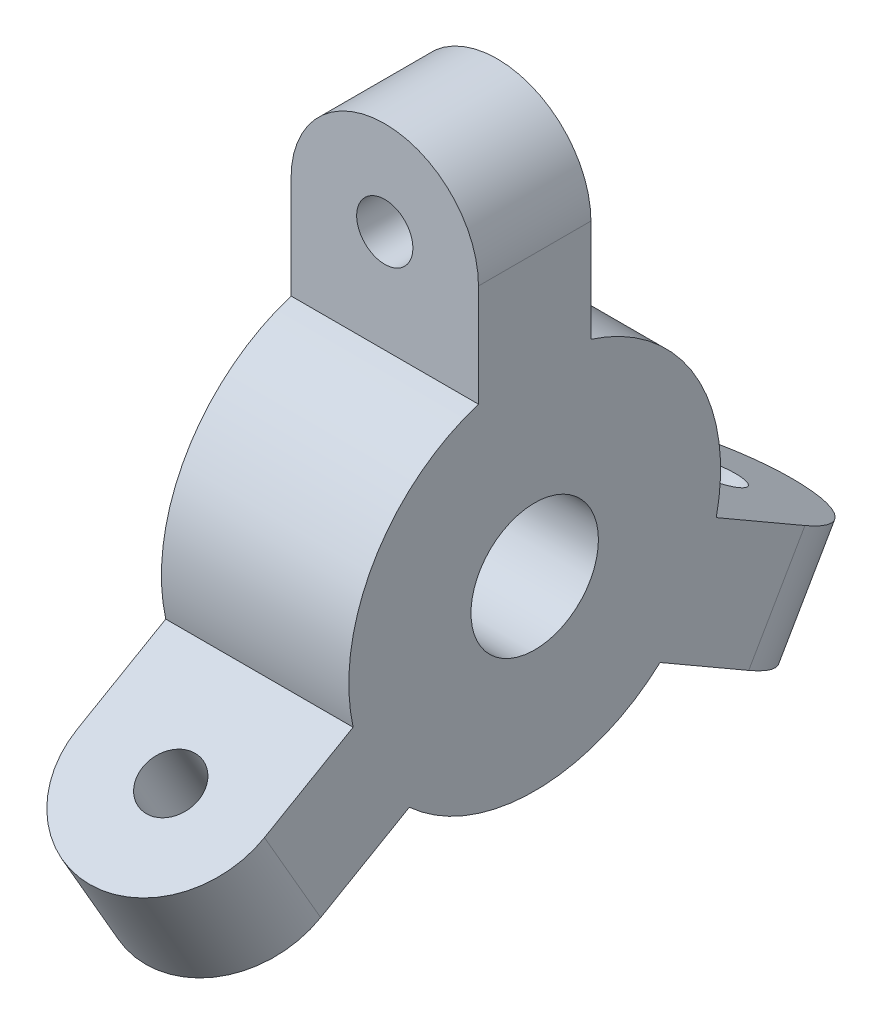
SolidWorks part; units mm, degrees
ref_plane "Plan de face" through (0, 0, 0) normal (0, 0, 1) x (1, 0, 0)
ref_plane "Plan de dessus" through (0, 0, 0) normal (0, 1, 0) x (1, 0, 0)
ref_plane "Plan de droite" through (0, 0, 0) normal (1, 0, 0) x (0, 0, -1)
sketch "Esquisse1" plane through (0, 0, 0) normal (1, 0, 0) x (0, 0, -1)
  line L0 (0, 0) -> (0, 19.92) construction
  line L1 (-3, 19.92) -> (3, 19.92)
  line L2 (-3, 19.92) -> (-3, 9.4555)
  line L3 (3, 19.92) -> (3, 9.4555)
  line L4 (18.7512, -7.3619) -> (9.6887, -2.1297)
  line L5 (18.7512, -7.3619) -> (15.7512, -12.5581)
  line L6 (15.7512, -12.5581) -> (6.6887, -7.3258)
  line L7 (-15.7512, -12.5581) -> (-6.6887, -7.3258)
  line L8 (-15.7512, -12.5581) -> (-18.7512, -7.3619)
  line L9 (-18.7512, -7.3619) -> (-9.6887, -2.1297)
  arc A0 (3, 9.4555) -> (9.6887, -2.1297) centre (0, 0) cw
  arc A1 (6.6887, -7.3258) -> (-6.6887, -7.3258) centre (0, 0) cw
  arc A2 (-9.6887, -2.1297) -> (-3, 9.4555) centre (0, 0) cw
  circle A3 centre (0, 0) radius 9.92 construction
  point P21 (0, 0)
  dimension "D4" = 9.92
  dimension "D1" = 19.92
  dimension "D2" = 6
  dimension "D3" = 3
extrude "Boss.-Extru.1" add sketch "Esquisse1" along normal blind 5 and the other way blind 5
hole_wizard "Trou taraudé M81" positions "Esquisse3" profile "Esquisse4" tap size "M8" standard "ISO" end condition through all
sketch "Esquisse3" plane through (5, 0, 0) normal (1, 0, 0) x (0, 0, -1)
  point P0 (0, 0)
sketch "Esquisse4" plane through (5, 0, 0) normal (0, 1, 0) x (0, 0, -1)
  line L0 (0, 0) -> (0, 10)
  line L1 (0, 10) -> (3.4, 10)
  line L2 (3.4, 10) -> (3.4, 0)
  line L5 (3.4, 0) -> (0, 0)
  line L11 (0, -6.35) -> (0, 107.95) construction
  dimension "Diamètre du trou pour taraudage jusqu'au prochain" = 6.8
  dimension "Profondeur du trou pour taraudage jusqu'au prochain" = 10
cosmetic thread "Filetage de perçage1" parameters "D2"=8
sketch "Esquisse5" plane through (0, 0, 3) normal (0, 0, 1) x (1, 0, 0)
  line L0 (0, 14.92) -> (0, 9.4555) construction
  line L1 (-5, 9.4555) -> (5, 9.4555) construction
  line L2 (-5, 9.4555) -> (-5, 14.92)
  line L3 (-5, 19.92) -> (-5, 9.4555) construction
  line L4 (-5, 9.4555) -> (-13.1992, 9.4555)
  line L5 (-13.1992, 9.4555) -> (-13.1992, 24.2674)
  line L6 (-13.1992, 24.2674) -> (13.6203, 24.2674)
  line L7 (13.6203, 24.2674) -> (13.6203, 9.4555)
  line L8 (13.6203, 9.4555) -> (5, 9.4555)
  line L9 (5, 9.4555) -> (5, 14.92)
  line L10 (5, 19.92) -> (5, 9.4555) construction
  line L11 (-5, 19.92) -> (5, 19.92) construction
  circle A0 centre (0, 14.92) radius 1.5
  arc A1 (-5, 14.92) -> (5, 14.92) centre (0, 14.92) cw
  dimension "D1" = 3
  dimension "D2" = 8.1992
  dimension "D3" = 8.6203
  dimension "D4" = 14.8119
extrude "Enlèv. mat.-Extru.1" cut sketch "Esquisse5" against normal through all
pattern_circular "Répétition circulaire1" count 3 over 360 about axis through (5, 0, 0) along (1, 0, 0) of "Enlèv. mat.-Extru.1"
